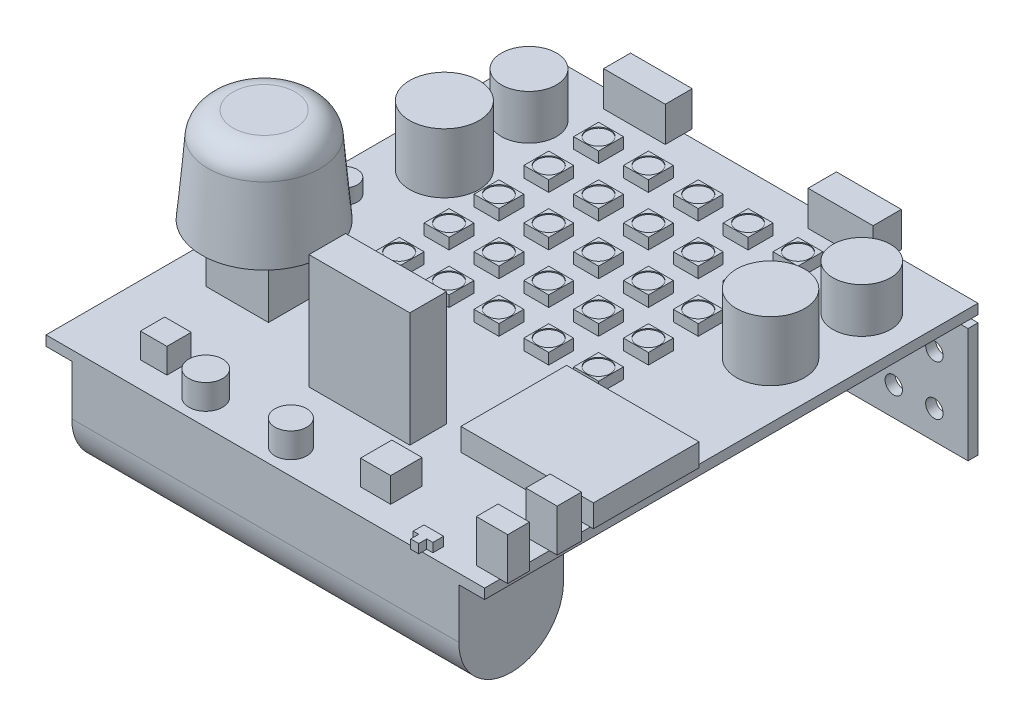
SolidWorks part; units mm, degrees
ref_plane "Plano frontal" through (0, 0, 0) normal (0, 0, 1) x (1, 0, 0)
ref_plane "Plano superior" through (0, 0, 0) normal (0, 1, 0) x (1, 0, 0)
ref_plane "Plano direito" through (0, 0, 0) normal (1, 0, 0) x (0, 0, -1)
sketch "Esboço1" plane through (0, 0, 0) normal (0, 1, 0) x (1, 0, 0)
  line L1 (-44, 49.5) -> (44, 49.5)
  line L2 (-44, 49.5) -> (-44, -49.5)
  line L3 (-44, -49.5) -> (44, -49.5)
  line L4 (44, 49.5) -> (44, -49.5)
  line L5 (-44, 49.5) -> (44, -49.5) construction
  line L6 (-44, -49.5) -> (44, 49.5) construction
  point P0 (0, 0)
  dimension "D1" = 88
  dimension "D2" = 99
extrude "Ressalto-extrusão1" add sketch "Esboço1" along normal blind 2
sketch "Esboço2" plane through (0, 0, 0) normal (1, 0, 0) x (0, 0, -1)
  line L0 (49.5, 0) -> (-49.5, 0) construction
  line L1 (49.5, -1.4) -> (47.5, -1.4)
  line L2 (49.5, -1.4) -> (49.5, -24.4)
  line L3 (49.5, -24.4) -> (47.5, -24.4)
  line L4 (47.5, -1.4) -> (47.5, -24.4)
  line L5 (49.5, 2) -> (49.5, 0) construction
  dimension "D1" = 23
  dimension "D2" = 1.4
  dimension "D3" = 2
extrude "Ressalto-extrusão2" add sketch "Esboço2" along normal mid plane 88 separate body
sketch "Esboço3" plane through (0, 0, 0) normal (1, 0, 0) x (0, 0, -1)
  line L0 (-49.5, 2) -> (-49.5, 0) construction
  line L1 (-28.5, 0) -> (-49.5, 0)
  line L2 (-28.5, 0) -> (-28.5, -10)
  line L3 (-28.5, -10) -> (-49.5, -10) construction
  line L4 (-49.5, 0) -> (-49.5, -10)
  line L5 (49.5, 0) -> (-49.5, 0) construction
  arc A0 (-49.5, -10) -> (-28.5, -10) centre (-39, -10) ccw
  dimension "D1" = 20.5
  dimension "D2" = 21
extrude "Ressalto-extrusão3" add sketch "Esboço3" along normal mid plane 77.66
sketch "Esboço4" plane through (0, 0, 0) normal (0, -1, 0) x (1, 0, 0)
  line L0 (-44, -49.5) -> (-44, 49.5) construction
  line L1 (-25.64, -25.7) -> (-23.28, -25.7)
  line L2 (-25.64, -25.7) -> (-25.64, -17.4)
  line L3 (-25.64, -17.4) -> (-23.28, -17.4)
  line L4 (-23.28, -25.7) -> (-23.28, -17.4)
  line L5 (44, -49.5) -> (-44, -49.5) construction
  dimension "D1" = 2.36
  dimension "D2" = 18.36
  dimension "D3" = 32.1
  dimension "D4" = 8.3
extrude "Ressalto-extrusão4" add sketch "Esboço4" along normal blind 9.4
sketch "Esboço5" plane through (0, 0, -49.5) normal (0, 0, -1) x (-1, 0, 0)
  line L0 (-44, -1.4) -> (44, -1.4) construction
  line L1 (-8.8037, -1.4) -> (5.0563, -1.4) construction
  line L2 (-8.8037, -1.4) -> (-8.8037, -19.1) construction
  line L3 (-8.8037, -19.1) -> (5.0563, -19.1) construction
  line L4 (5.0563, -1.4) -> (5.0563, -19.1) construction
  line L5 (-44, -24.4) -> (44, -24.4) construction
  line L6 (5.0563, -1.4) -> (5.0563, -16.0436)
  line L7 (1.9255, -19.1) -> (-5.7473, -19.1)
  line L8 (-8.8037, -16.0436) -> (-8.8037, -1.4)
  line L9 (-8.8037, -1.4) -> (5.0563, -1.4)
  arc A0 (5.0563, -16.0436) -> (1.9255, -19.1) centre (1.9989, -16.0436) cw
  arc A1 (-5.7473, -19.1) -> (-8.8037, -16.0436) centre (-5.7473, -16.0436) cw
  dimension "D1" = 13.86
  dimension "D2" = 5.3
extrude "Corte-extrusão1" cut sketch "Esboço5" against normal up to surface (2 mm away) up to face at (0, -12.9, -47.5)
sketch "Esboço6" plane through (0, 2, 0) normal (0, 1, 0) x (1, 0, 0)
  line L0 (32.6827, -46.3971) -> (28.7439, -46.3971)
  line L1 (18.0257, -28.2797) -> (44.6149, -28.2797)
  line L2 (18.0257, -28.2797) -> (18.0257, -7.0704)
  line L3 (18.0257, -7.0704) -> (44.6149, -7.0704)
  line L4 (44.6149, -28.2797) -> (44.6149, -7.0704)
  line L5 (-8.5589, -32.1706) -> (11.6709, -32.1706)
  line L6 (-8.5589, -32.1706) -> (-8.5589, -24.8328)
  line L7 (-8.5589, -24.8328) -> (11.6709, -24.8328)
  line L8 (11.6709, -32.1706) -> (11.6709, -24.8328)
  line L9 (39.2386, -31.5921) -> (45.5361, -31.5921)
  line L10 (39.2386, -31.5921) -> (39.2386, -36.4781)
  line L11 (39.2386, -36.4781) -> (45.5361, -36.4781)
  line L12 (45.5361, -31.5921) -> (45.5361, -36.4781)
  line L13 (39.2386, -42.025) -> (45.5361, -42.025)
  line L14 (39.2386, -42.025) -> (39.2386, -46.3971)
  line L15 (39.2386, -46.3971) -> (45.5361, -46.3971)
  line L16 (45.5361, -42.025) -> (45.5361, -46.3971)
  line L17 (27.0027, 51.1135) -> (13.9719, 51.1135)
  line L18 (27.0027, 51.1135) -> (27.0027, 45.4384)
  line L19 (27.0027, 45.4384) -> (13.9719, 45.4384)
  line L20 (13.9719, 51.1135) -> (13.9719, 45.4384)
  line L21 (-27.3276, 51.1135) -> (-14.9516, 51.1135)
  line L22 (-27.3276, 51.1135) -> (-27.3276, 45.7047)
  line L23 (-27.3276, 45.7047) -> (-14.9516, 45.7047)
  line L24 (-14.9516, 51.1135) -> (-14.9516, 45.7047)
  line L25 (-30.1915, -39.4874) -> (-24.874, -39.4874)
  line L26 (-30.1915, -39.4874) -> (-30.1915, -44.366)
  line L27 (-30.1915, -44.366) -> (-24.874, -44.366)
  line L28 (-24.874, -39.4874) -> (-24.874, -44.366)
  line L29 (20.0285, -38.0781) -> (13.9719, -38.0781)
  line L30 (20.0285, -38.0781) -> (20.0285, -44.366)
  line L31 (20.0285, -44.366) -> (13.9719, -44.366)
  line L32 (13.9719, -38.0781) -> (13.9719, -44.366)
  line L33 (3.9372, -19.5354) -> (-0.7319, -19.5354)
  line L34 (3.9372, -19.5354) -> (3.9372, -23.5944)
  line L35 (3.9372, -23.5944) -> (-0.7319, -23.5944)
  line L36 (-0.7319, -19.5354) -> (-0.7319, -23.5944)
  line L37 (28.7439, -46.3971) -> (28.7439, -48.5611)
  line L38 (28.7439, -48.5611) -> (29.8392, -48.5611)
  line L39 (29.8392, -48.5611) -> (29.8392, -50.1607)
  line L40 (29.8392, -50.1607) -> (31.4501, -50.1607)
  line L41 (31.4501, -50.1607) -> (31.4501, -48.5611)
  line L42 (31.4501, -48.5611) -> (32.6827, -48.5611)
  line L43 (32.6827, -48.5611) -> (32.6827, -46.3971)
  line L45 (-23.8209, -13.9452) -> (-36.3296, -13.9452)
  line L46 (-23.8209, -13.9452) -> (-23.8209, -25.0355)
  line L47 (-23.8209, -25.0355) -> (-36.3296, -25.0355)
  line L48 (-36.3296, -13.9452) -> (-36.3296, -25.0355)
  circle A0 centre (-30.1915, -19.5354) radius 12.5
  circle A1 centre (-32.7572, 36.1666) radius 5.5325
  circle A2 centre (-32.7572, 19.1926) radius 6.9615
  circle A3 centre (34.0069, 36.1666) radius 5.7996
  circle A4 centre (32.6827, 19.1926) radius 6.8523
  circle A5 centre (-38.489, 4.8117) radius 2.6498
  circle A6 centre (-17.0815, -44.366) radius 3.3863
  circle A7 centre (0, -44.366) radius 3.2014
  dimension "D1" = 25
extrude "Ressalto-extrusão5" add sketch "Esboço6" along normal blind 19 draft 5 from offset 12 contours A0
extrude "Ressalto-extrusão6" add sketch "Esboço6<3>" along normal blind 23 contours L7 L8 L5 L6
sketch "Esboço6<3>" plane through (0, 2, 0) normal (0, 1, 0) x (1, 0, 0) same geometry as "Esboço6"
extrude "Ressalto-extrusão7" add sketch "Esboço6<4>" along normal blind 12 contours A2 | A4
sketch "Esboço6<4>" plane through (0, 2, 0) normal (0, 1, 0) x (1, 0, 0) same geometry as "Esboço6"
extrude "Ressalto-extrusão8" add sketch "Esboço6<5>" along normal blind 9 contours A1 | A3
sketch "Esboço6<5>" plane through (0, 2, 0) normal (0, 1, 0) x (1, 0, 0) same geometry as "Esboço6"
extrude "Ressalto-extrusão9" add sketch "Esboço6<6>" along normal blind 3 contours A5
sketch "Esboço6<6>" plane through (0, 2, 0) normal (0, 1, 0) x (1, 0, 0) same geometry as "Esboço6"
extrude "Ressalto-extrusão10" add sketch "Esboço6<7>" along normal blind 7 contours L22 L23 L24 L21 | L20 L19 L18 L17
sketch "Esboço6<7>" plane through (0, 2, 0) normal (0, 1, 0) x (1, 0, 0) same geometry as "Esboço6"
extrude "Ressalto-extrusão11" add sketch "Esboço6<8>" along normal blind 4.5 contours L2 L3 L4 L1
sketch "Esboço6<8>" plane through (0, 2, 0) normal (0, 1, 0) x (1, 0, 0) same geometry as "Esboço6"
fillet "Filete1" radius 5 1 edges at (-30.1915, 33, 30.3731)
extrude "Ressalto-extrusão12" add sketch "Esboço6<9>" along normal blind 8.5 contours L10 L11 L12 L9 | L14 L15 L16 L13
sketch "Esboço6<9>" plane through (0, 2, 0) normal (0, 1, 0) x (1, 0, 0) same geometry as "Esboço6"
extrude "Ressalto-extrusão13" add sketch "Esboço6<10>" along normal blind 5 contours L26 L27 L28 L25 | A6 | A7 | L32 L31 L30 L29
sketch "Esboço6<10>" plane through (0, 2, 0) normal (0, 1, 0) x (1, 0, 0) same geometry as "Esboço6"
extrude "Ressalto-extrusão14" add sketch "Esboço6<11>" along normal blind 1.8 contours L37 L38 L39 L40 L41 L42 L43 L0 | L36 L35 L34 L33
sketch "Esboço6<11>" plane through (0, 2, 0) normal (0, 1, 0) x (1, 0, 0) same geometry as "Esboço6"
sketch "Esboço7" plane through (0, 2, 0) normal (0, 1, 0) x (1, 0, 0)
  line L1 (21.6909, 40.6784) -> (16.6909, 40.6784)
  line L2 (21.6909, 40.6784) -> (21.6909, 35.6784)
  line L3 (21.6909, 35.6784) -> (16.6909, 35.6784)
  line L4 (16.6909, 40.6784) -> (16.6909, 35.6784)
  dimension "D1" = 5
  dimension "D2" = 5
extrude "Ressalto-extrusão15" add sketch "Esboço7" along normal blind 2.2
sketch "Esboço8" plane through (0, 4.2, 0) normal (0, 1, 0) x (1, 0, 0)
  line L6 (21.6909, 35.6784) -> (16.6909, 40.6784) construction
  line L7 (16.6909, 35.6784) -> (21.6909, 40.6784) construction
  circle A0 centre (19.1909, 38.1784) radius 2.35
  dimension "D1" = 4.7
extrude "Corte-extrusão2" cut sketch "Esboço8" against normal blind 0.2
pattern_linear "Padrão linear1" count 5 spacing 10 along (0, 0, 1) count 5 spacing 10 along (-1, 0, 0) of "Ressalto-extrusão15", "Corte-extrusão2"
extrude "Ressalto-extrusão16" add sketch "Esboço6<12>" along normal blind 20 contours L48 L47 L46 L45
sketch "Esboço6<12>" plane through (0, 2, 0) normal (0, 1, 0) x (1, 0, 0) same geometry as "Esboço6"
sketch "Esboço9" plane through (0, 0, -49.5) normal (0, 0, -1) x (-1, 0, 0)
  line L0 (40.33, -20.4) -> (40.33, -24.4) construction
  line L1 (-44, -24.4) -> (44, -24.4) construction
  line L2 (42.08, -18.65) -> (44, -18.65) construction
  line L3 (44, -24.4) -> (44, -1.4) construction
  circle A0 centre (40.33, -18.65) radius 1.75
  dimension "D1" = 3.5
  dimension "D2" = 4
  dimension "D3" = 1.92
extrude "Corte-extrusão3" cut sketch "Esboço9" against normal up to next (2 mm away)
pattern_linear "Padrão linear2" count 5 spacing 7.25 along (1, 0, 0) count 2 spacing 10 along (0, 1, 0) of "Corte-extrusão3"
sketch "Esboço10" plane through (0, 0, -49.5) normal (0, 0, -1) x (-1, 0, 0)
  line L0 (-37.25, -20.4) -> (-37.25, -24.4) construction
  line L1 (-44, -24.4) -> (44, -24.4) construction
  line L2 (-39, -18.65) -> (-44, -18.65) construction
  line L3 (-44, -24.4) -> (-44, -1.4) construction
  circle A0 centre (-37.25, -18.65) radius 1.75
  dimension "D1" = 3.5
  dimension "D2" = 4
  dimension "D3" = 5
extrude "Corte-extrusão4" cut sketch "Esboço10" against normal up to next (2 mm away)
pattern_linear "Padrão linear3" count 4 spacing 8.15 along (-1, 0, 0) count 2 spacing 10 along (0, 1, 0) of "Corte-extrusão4"
